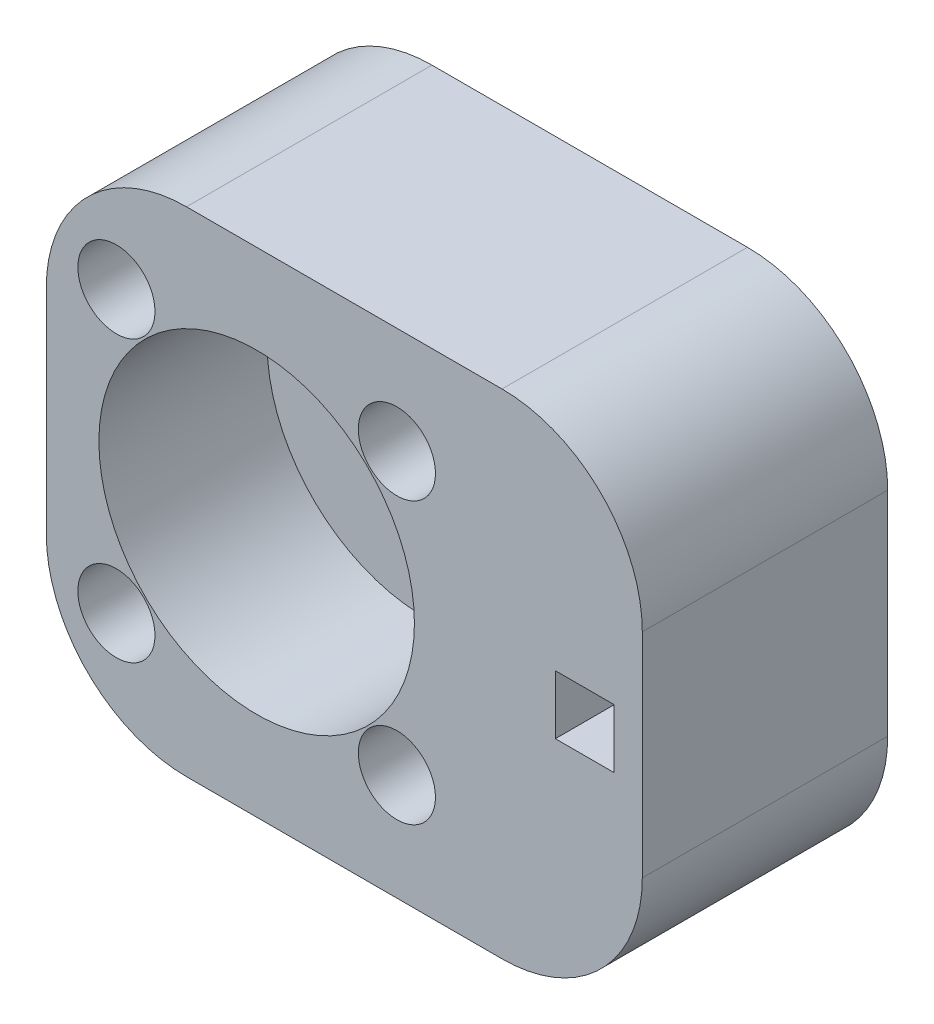
SolidWorks part; units mm, degrees
ref_plane "Front Plane" through (0, 0, 0) normal (0, 0, 1) x (1, 0, 0)
ref_plane "Top Plane" through (0, 0, 0) normal (0, 1, 0) x (1, 0, 0)
ref_plane "Right Plane" through (0, 0, 0) normal (1, 0, 0) x (0, 0, -1)
sketch "Sketch1" plane through (0, 0, 0) normal (0, 0, 1) x (1, 0, 0)
  line L0 (-108.4821, -31.2203) -> (-81.0821, -31.2203) construction
  line L4 (-67.2821, -13.6231) -> (-109.7821, -13.6231)
  line L5 (-67.2821, -13.6231) -> (-67.2821, -48.8175)
  line L6 (-67.2821, -48.8175) -> (-109.7821, -48.8175)
  line L7 (-109.7821, -13.6231) -> (-109.7821, -48.8175)
  point P6 (-94.7821, -31.2203)
  dimension "D1" = 42.5
  dimension "D2" = 15
extrude "Boss-Extrude1" add sketch "Sketch1" along normal blind 17.5 contours L6 L7 L4 L5
sketch "Sketch3" plane through (0, 0, 17.5) normal (0, 0, 1) x (1, 0, 0)
  line L0 (-67.2821, -31.2203) -> (6.1928, -31.2203) construction
  line L1 (-67.2821, -13.6231) -> (-67.2821, -48.8175) construction
  line L3 (-69.2821, -33.3203) -> (-73.4821, -33.3203)
  line L4 (-69.2821, -33.3203) -> (-69.2821, -29.1203)
  line L5 (-69.2821, -29.1203) -> (-73.4821, -29.1203)
  line L6 (-73.4821, -33.3203) -> (-73.4821, -29.1203)
  line L7 (-69.2821, -33.3203) -> (-73.4821, -29.1203) construction
  line L8 (-69.2821, -29.1203) -> (-73.4821, -33.3203) construction
  point P4 (-71.3821, -31.2203)
  dimension "D1" = 4.2
  dimension "D2" = 2
extrude "Cut-Extrude1" cut sketch "Sketch3" against normal offset from surface (12.5 mm away) 5 up to face at (-88.5321, -31.2203, 0)
sketch "Sketch4" plane through (0, 0, 17.5) normal (0, 0, 1) x (1, 0, 0)
  circle A8 centre (-84.7821, -21.2203) radius 1.6 construction
  circle A9 centre (-84.7821, -41.2203) radius 1.6 construction
  circle A10 centre (-104.7821, -21.2203) radius 1.6 construction
  circle A11 centre (-104.7821, -41.2203) radius 1.6 construction
  circle A12 centre (-84.7821, -21.2203) radius 1.6
  circle A13 centre (-84.7821, -41.2203) radius 1.6
  circle A14 centre (-104.7821, -21.2203) radius 1.6
  circle A15 centre (-104.7821, -41.2203) radius 1.6
extrude "Cut-Extrude2" cut sketch "Sketch4" against normal through all
sketch "Sketch5" plane through (0, 0, 17.5) normal (0, 0, 1) x (1, 0, 0)
  circle A0 centre (-84.7821, -41.2203) radius 2.75
  circle A1 centre (-84.7821, -21.2203) radius 2.75
  circle A2 centre (-104.7821, -21.2203) radius 2.75
  circle A3 centre (-104.7821, -41.2203) radius 2.75
  dimension "D1" = 5.5
extrude "Cut-Extrude3" cut sketch "Sketch5" against normal offset from surface (15 mm away) 2.5 up to face at (-83.1821, -41.2203, 0)
sketch "Sketch6" plane through (0, 0, 17.5) normal (0, 0, 1) x (1, 0, 0)
  line L0 (-81.0821, -8.5203) -> (-108.4821, -8.5203) construction
  line L2 (-81.0821, -8.5203) -> (-108.4821, -8.5203) construction
  line L8 (-104.7821, -21.2203) -> (-84.7821, -41.2203) construction
  line L9 (-104.7821, -41.2203) -> (-84.7821, -21.2203) construction
  circle A0 centre (-94.7821, -31.2203) radius 11.25
  dimension "D1" = 22.5
extrude "Cut-Extrude4" cut sketch "Sketch6" against normal blind 12
fillet "Fillet1" radius 10 4 edges at (-109.7821, -48.8175, 8.75) (-109.7821, -13.6231, 8.75) (-67.2821, -13.6231, 8.75) (-67.2821, -48.8175, 8.75)
